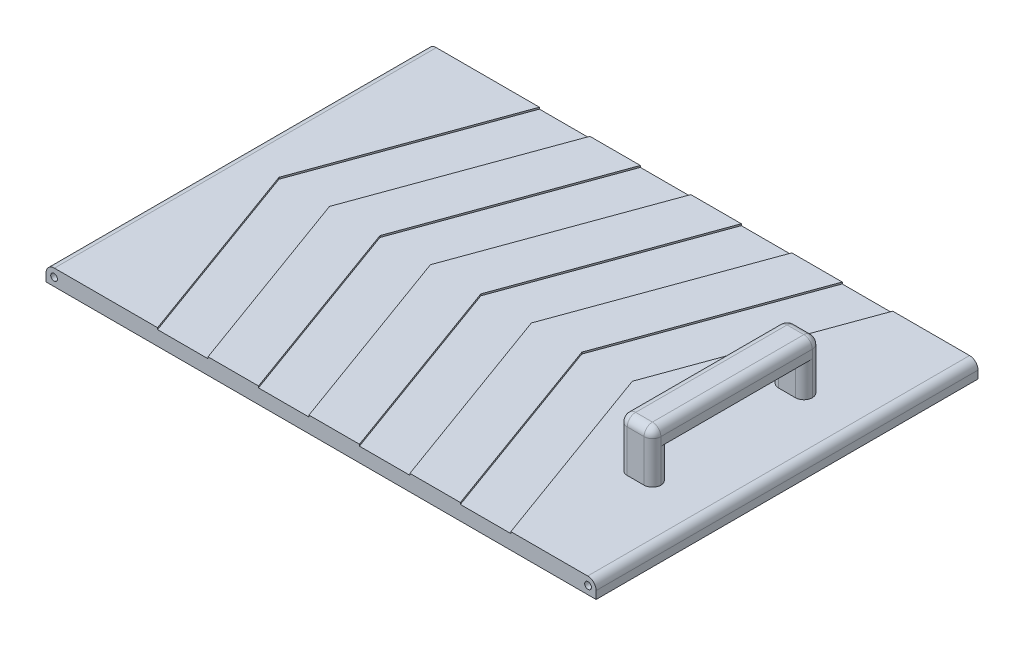
SolidWorks part; units mm, degrees
ref_plane "Plano frontal" through (0, 0, 0) normal (0, 0, 1) x (1, 0, 0)
ref_plane "Plano superior" through (0, 0, 0) normal (0, 1, 0) x (1, 0, 0)
ref_plane "Plano direito" through (0, 0, 0) normal (1, 0, 0) x (0, 0, -1)
sketch "Esboço1" plane through (0, 0, 0) normal (0, 1, 0) x (1, 0, 0)
  line L0 (-81.75, -56.75) -> (-81.75, 56.75)
  line L1 (80, -55) -> (-80, -55)
  line L2 (80, -55) -> (80, 55)
  line L3 (80, 55) -> (-80, 55)
  line L4 (-80, -55) -> (-80, 55)
  line L5 (80, -55) -> (-80, 55) construction
  line L6 (80, 55) -> (-80, -55) construction
  line L7 (81.75, 56.75) -> (-81.75, 56.75)
  line L8 (81.75, -56.75) -> (81.75, 56.75)
  line L9 (81.75, -56.75) -> (-81.75, -56.75)
  point P0 (0, 0)
  dimension "D1" = 160
  dimension "D2" = 110
  dimension "D3" = 1.75
extrude "Ressalto-extrusão1" add sketch "Esboço1" along normal blind 4.8 contours L4 L1 L2 L3 | L9 L8 L7 L0 L1 L4 L3 L2 region at (-81.551, 0, 0) region at (0, 0, 0)
sketch "Esboço2" plane through (0, 0, 56.75) normal (0, 0, 1) x (1, 0, 0)
  line L0 (0, 0) -> (0, 4.8) construction
  line L1 (81.75, 4.8) -> (-81.75, 4.8) construction
  line L2 (79.35, 2.4) -> (-79.35, 2.4)
  line L3 (-79.35, 2.4) -> (-81.75, 4.8) construction
  circle A0 centre (-79.35, 2.4) radius 1
  circle A1 centre (79.35, 2.4) radius 1
  point P8 (0, 2.4)
  dimension "D1" = 2
  dimension "D3" = 2
  dimension "D2" = 45
extrude "Corte-extrusão1" cut sketch "Esboço2" against normal blind 20 contours A1 | A0
mirror "Espelhar1" about plane through (0, 0, 0) normal (0, 0, 1) of "Corte-extrusão1"
fillet "Filete1" radius 2.5 2 edges at (-81.75, 4.8, 0) (81.75, 4.8, 0)
sketch "Esboço3" plane through (0, 4.8, 0) normal (0, 1, 0) x (1, 0, 0)
  line L0 (81.75, 0) -> (61.75, 0) construction
  line L1 (81.75, 56.75) -> (81.75, -56.75) construction
  line L3 (56.75, 25) -> (66.75, 25) construction
  line L4 (56.75, 25) -> (56.75, -25) construction
  line L5 (56.75, -25) -> (66.75, -25) construction
  line L6 (66.75, 25) -> (66.75, -25) construction
  line L7 (56.75, 25) -> (66.75, -25) construction
  line L8 (56.75, -25) -> (66.75, 25) construction
  line L9 (66.75, -25) -> (56.75, -25)
  line L10 (66.75, -25) -> (66.75, -20)
  line L11 (66.75, -20) -> (56.75, -20)
  line L12 (56.75, -25) -> (56.75, -20)
  line L13 (66.75, 25) -> (56.75, 25)
  line L14 (66.75, 25) -> (66.75, 20)
  line L15 (66.75, 20) -> (56.75, 20)
  line L16 (56.75, 25) -> (56.75, 20)
  dimension "D1" = 5
  dimension "D2" = 15
  dimension "D3" = 10
  dimension "D4" = 50
extrude "Ressalto-extrusão2" add sketch "Esboço3" along normal blind 10
sketch "Esboço4" plane through (0, 14.8, 0) normal (0, 1, 0) x (1, 0, 0)
  line L1 (66.75, -25) -> (56.75, -25)
  line L2 (66.75, -25) -> (66.75, 25)
  line L3 (66.75, 25) -> (56.75, 25)
  line L4 (56.75, -25) -> (56.75, 25)
extrude "Ressalto-extrusão3" add sketch "Esboço4" along normal blind 5
fillet "Filete2" radius 2.5 2 edges at (61.75, 19.8, 25) (61.75, 19.8, -25)
fillet "Filete3" radius 2.5 14 edges at (56.75, 11.05, -25) (56.75, 19.0678, -24.2678) (56.75, 11.05, 25) (56.75, 19.0678, 24.2678) (66.75, 11.05, 25) (66.75, 19.0678, 24.2678) (66.75, 11.05, -25) (66.75, 19.0678, -24.2678) (56.75, 19.8, 0) (66.75, 19.8, 0) (66.75, 9.8, 20) (56.75, 9.8, 20) (56.75, 9.8, -20) (66.75, 9.8, -20)
sketch "Esboço5" plane through (0, 4.8, 0) normal (0, 1, 0) x (1, 0, 0)
  line L0 (0, 0) -> (-81.75, 0) construction
  line L1 (-81.75, -56.75) -> (-81.75, 56.75) construction
  line L2 (-54.25, 0) -> (-32.4118, 60)
  line L3 (-32.4118, 60) -> (-47.4118, 60)
  line L4 (-47.4118, 60) -> (-69.25, 0)
  line L5 (-54.25, 0) -> (-32.4118, -60)
  line L6 (-32.4118, -60) -> (-47.4118, -60)
  line L7 (-47.4118, -60) -> (-69.25, 0)
  line L8 (-79.25, 56.75) -> (-79.25, -56.75) construction
  line L9 (-24.25, 0) -> (-2.4118, -60)
  line L10 (-17.4118, -60) -> (-39.25, 0)
  line L11 (-2.4118, -60) -> (-17.4118, -60)
  line L12 (-17.4118, 60) -> (-39.25, 0)
  line L13 (-2.4118, 60) -> (-17.4118, 60)
  line L14 (-24.25, 0) -> (-2.4118, 60)
  line L15 (5.75, 0) -> (27.5882, -60)
  line L16 (12.5882, -60) -> (-9.25, 0)
  line L17 (27.5882, -60) -> (12.5882, -60)
  line L18 (12.5882, 60) -> (-9.25, 0)
  line L19 (27.5882, 60) -> (12.5882, 60)
  line L20 (5.75, 0) -> (27.5882, 60)
  line L21 (35.75, 0) -> (57.5882, -60)
  line L22 (42.5882, -60) -> (20.75, 0)
  line L23 (57.5882, -60) -> (42.5882, -60)
  line L24 (42.5882, 60) -> (20.75, 0)
  line L25 (57.5882, 60) -> (42.5882, 60)
  line L26 (35.75, 0) -> (57.5882, 60)
  line L27 (-43.3309, -30) -> (-28.3309, -30) construction
  dimension "D1" = 70
  dimension "D2" = 70
  dimension "D3" = 60
  dimension "D4" = 15
  dimension "D5" = 10
  dimension "D7" = 15
  dimension "D6" = 4
extrude "Corte-extrusão2" cut sketch "Esboço5" against normal blind 0.5
